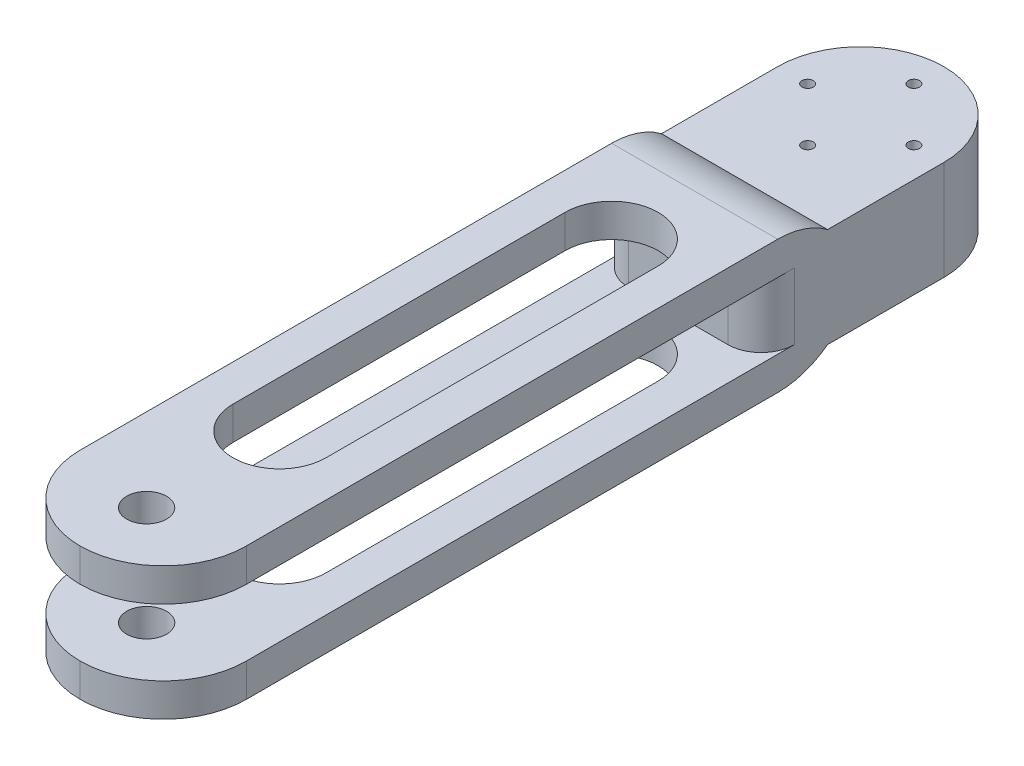
SolidWorks part; units mm, degrees
ref_plane "Plan de face" through (0, 0, 0) normal (0, 0, 1) x (1, 0, 0)
ref_plane "Plan de dessus" through (0, 0, 0) normal (0, 1, 0) x (1, 0, 0)
ref_plane "Plan de droite" through (0, 0, 0) normal (1, 0, 0) x (0, 0, -1)
sketch "Esquisse1" plane through (0, 0, 0) normal (1, 0, 0) x (0, 0, -1)
  line L0 (90, 10) -> (-10, 10)
  line L1 (-10, 10) -> (-10, 5)
  line L2 (90, 10) -> (90, 7.5)
  line L3 (90, 7.5) -> (120, 7.5)
  line L4 (-10, 5) -> (80, 5)
  line L5 (80, 5) -> (80, -5)
  line L6 (120, 7.5) -> (120, -7.5)
  line L7 (55, 0) -> (-55, 0) construction
  line L8 (-10, -5) -> (80, -5)
  line L9 (90, -7.5) -> (120, -7.5)
  line L10 (90, -10) -> (90, -7.5)
  line L11 (-10, -10) -> (-10, -5)
  line L12 (90, -10) -> (-10, -10)
  point P12 (120, 0)
  point P13 (80, 0)
  dimension "D1" = 130
  dimension "10" = 10
  dimension "D2" = 15
  dimension "D3" = 5
  dimension "D4" = 10
  dimension "D5" = 10
  dimension "D6" = 80
extrude "Boss.-Extru.1" add sketch "Esquisse1" along normal mid plane 25
fillet "Congé1" radius 12.5 8 edges at (0, -10, -90) (0, 10, -90) (-12.5, -7.5, 10) (-12.5, 7.5, 10) (12.5, -7.5, 10) (12.5, 7.5, 10) (-12.5, 0, -120) (12.5, 0, -120)
sketch "Esquisse2" plane through (0, 7.5, 0) normal (0, 1, 0) x (1, 0, 0)
  line L0 (-12.5, 107.5) -> (12.5, 107.5) construction
  line L1 (0, 120) -> (0, 226.6844) construction
  arc A0 (0, 120) -> (-12.5, 107.5) centre (0, 107.5) ccw construction
  circle A1 centre (8, 107.5) radius 0.85
  circle A2 centre (0, 115.5) radius 0.85
  circle A3 centre (-8, 107.5) radius 0.85
  circle A4 centre (0, 99.5) radius 0.85
  point P12 (0, 173.3422)
  dimension "D1" = 1.7
  dimension "D2" = 1.7
  dimension "D3" = 8
  dimension "D4" = 8
extrude "Enlèv. mat.-Extru.1" cut sketch "Esquisse2" against normal through all
sketch "Esquisse3" plane through (0, 10, 0) normal (0, 1, 0) x (1, 0, 0)
  circle A0 centre (0, 0) radius 3
  dimension "D1" = 6
extrude "Enlèv. mat.-Extru.2" cut sketch "Esquisse3" against normal through all
sketch "Esquisse4" plane through (0, 10, 0) normal (0, 1, 0) x (1, 0, 0)
  line L0 (-7, 70) -> (-7, 20)
  line L1 (0, -11) -> (0, 11) construction
  line L2 (7, 70) -> (7, 20)
  arc A0 (-7, 20) -> (7, 20) centre (0, 20) ccw
  arc A1 (-7, 70) -> (7, 70) centre (0, 70) cw
  dimension "D1" = 7
  dimension "D2" = 20
  dimension "D3" = 70
extrude "Enlèv. mat.-Extru.3" cut sketch "Esquisse4" against normal through all
fillet "Congé2" radius 5 2 edges at (-12.5, 0, -80) (12.5, 0, -80)
